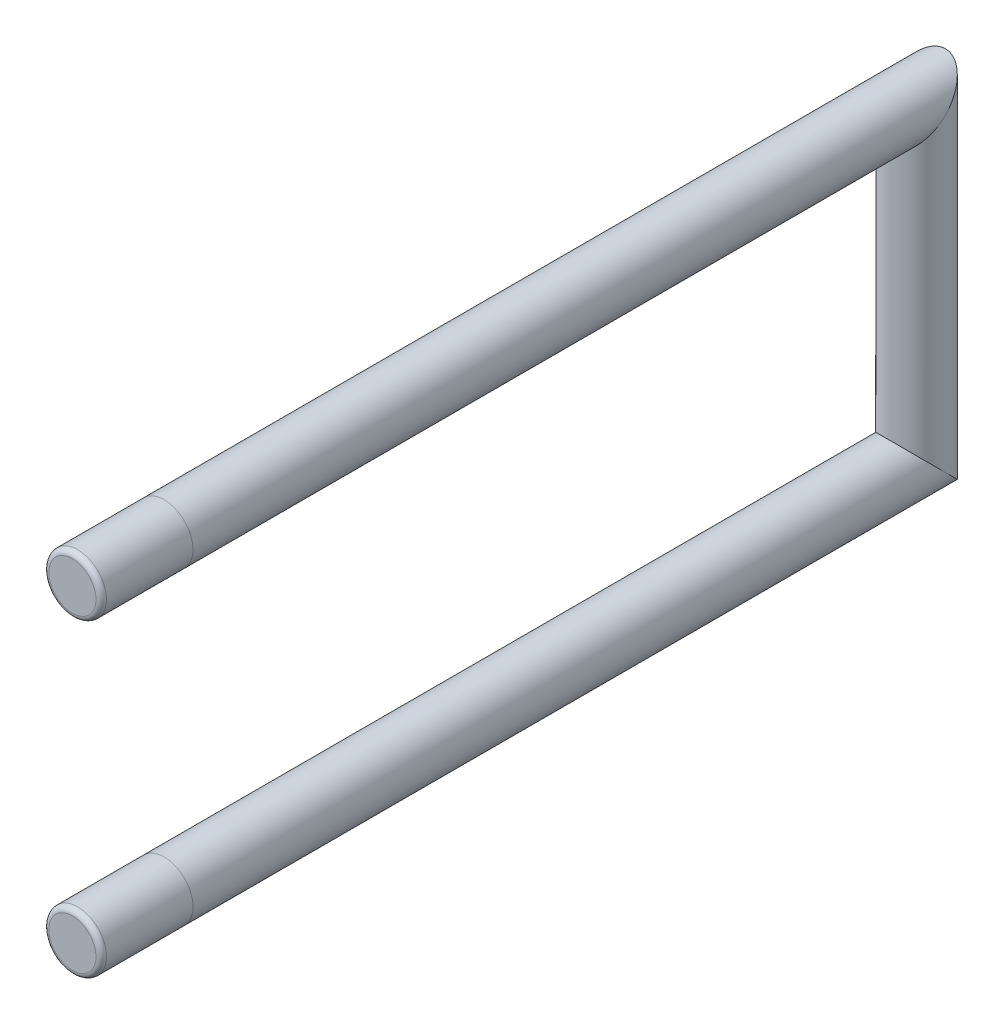
SolidWorks part; units mm, degrees
ref_plane "前视基准面" through (0, 0, 0) normal (0, 0, 1) x (1, 0, 0)
ref_plane "上视基准面" through (0, 0, 0) normal (0, 1, 0) x (1, 0, 0)
ref_plane "右视基准面" through (0, 0, 0) normal (1, 0, 0) x (0, 0, -1)
sketch "草图1" plane through (0, 0, 0) normal (0, 0, 1) x (1, 0, 0)
  circle A0 centre (0, 0) radius 11
  dimension "D1" = 22
extrude "拉伸1" add sketch "草图1" along normal blind 287
sketch "草图2" plane through (0, 0, 0) normal (0, 1, 0) x (1, 0, 0)
  circle A0 centre (0, 0) radius 11
  dimension "D1" = 22
extrude "拉伸2" add sketch "草图2" along normal blind 118
ref_axis "基准轴1" through (0, 136.0544, 0) along (0, -1, 0)
pattern_linear "阵列(线性)1" count 2 spacing 118 along (0, 1, 0) of "拉伸1"
chamfer "倒角3" distance 21.999 angle 45 2 edges at (0, 0, 0) (0, 118, 0)
sketch "草图3" plane through (0, 0, 287) normal (0, 0, 1) x (1, 0, 0)
  circle A0 centre (0, 118) radius 10.9995
  circle A1 centre (0, 0) radius 10.9995
  circle A2 centre (0, 118) radius 11 construction
  dimension "D1" = 21.999
extrude "拉伸3" add sketch "草图3" along normal blind 35
fillet "圆角1" radius 2 2 edges at (10.9995, 0, 322) (10.9995, 118, 322)
